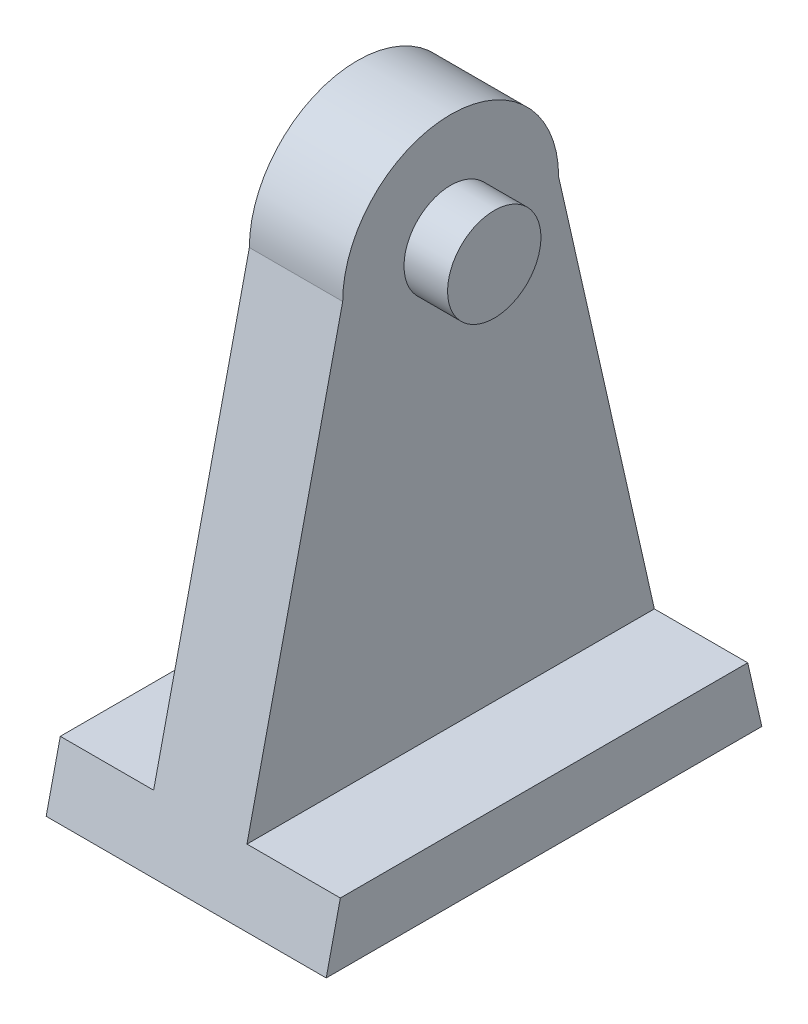
SolidWorks part; units mm, degrees
ref_plane "Front Plane" through (0, 0, 0) normal (0, 0, 1) x (1, 0, 0)
ref_plane "Top Plane" through (0, 0, 0) normal (0, 1, 0) x (1, 0, 0)
ref_plane "Right Plane" through (0, 0, 0) normal (1, 0, 0) x (0, 0, -1)
sketch "Sketch1" plane through (0, 0, 0) normal (1, 0, 0) x (0, 0, -1)
  line L0 (-17.35, 77.82) -> (-35, 0)
  line L1 (-35, 0) -> (35, 0)
  line L2 (0, 77.82) -> (0, -75.9186) construction
  line L3 (17.35, 77.82) -> (35, 0)
  line L4 (-32.7319, 10) -> (32.7319, 10)
  circle A0 centre (0, 77.82) radius 17.35
  circle A1 centre (0, 77.82) radius 7.5
  point P7 (0, 0)
  dimension "D1" = 77.82
  dimension "D2" = 34.7
  dimension "D5" = 15
  dimension "D3" = 35
  dimension "D4" = 10
extrude "Boss-Extrude1" add sketch "Sketch1" along normal mid plane 15 contours L2 A0 L0 L4 | A0 L2 L4 L3 | L2 L4 L0 L1 | L4 L2 L1 L3 | A1 A0 | A1 region at (0, 35.5836, 13.8119) region at (0, 82.9733, 5.1533) region at (0, 94.6793, 0) region at (0, 4.9442, 16.9393) region at (0, 35.5836, -13.8119) region at (0, 4.9442, -16.9393)
extrude "Boss-Extrude2" add sketch "Sketch1<3>" along normal mid plane 45 contours L2 L4 L0 L1 | L4 L2 L1 L3 region at (0, 4.9442, 16.9393) region at (0, 4.9442, -16.9393)
sketch "Sketch1<3>" plane through (0, 0, 0) normal (1, 0, 0) x (0, 0, -1) same geometry as "Sketch1"
extrude "Boss-Extrude3" add sketch "Sketch1<4>" along normal blind 14.5 contours A1
sketch "Sketch1<4>" plane through (0, 0, 0) normal (1, 0, 0) x (0, 0, -1) same geometry as "Sketch1"
